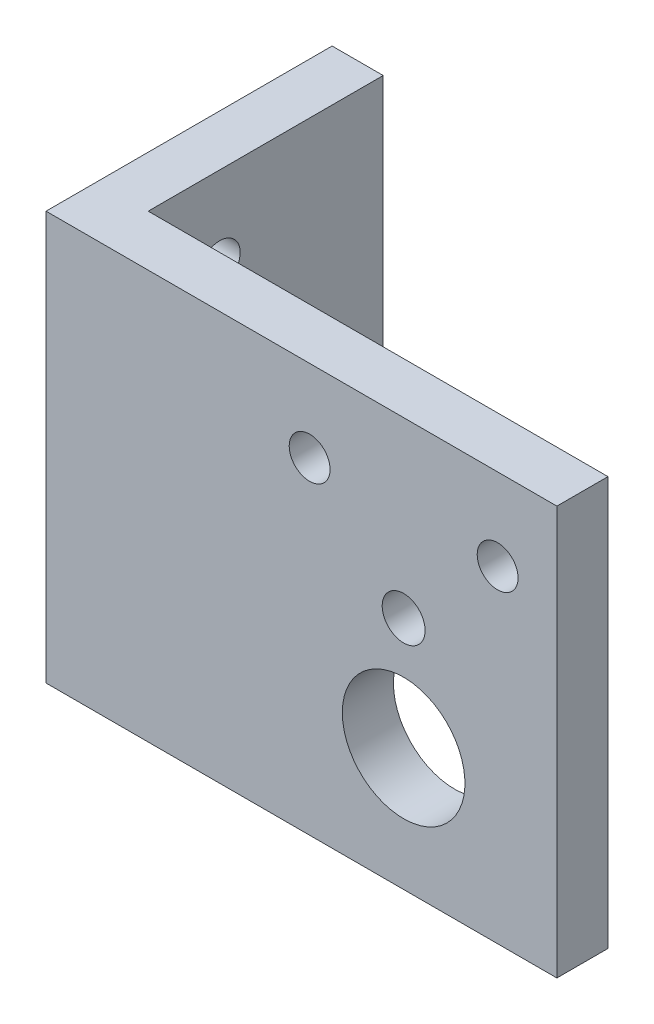
SolidWorks part; units mm, degrees
ref_plane "Front Plane" through (0, 0, 0) normal (0, 0, 1) x (1, 0, 0)
ref_plane "Top Plane" through (0, 0, 0) normal (0, 1, 0) x (1, 0, 0)
ref_plane "Right Plane" through (0, 0, 0) normal (1, 0, 0) x (0, 0, -1)
sketch "Sketch1" plane through (0, 0, 0) normal (0, 1, 0) x (1, 0, 0)
  line L0 (0, 0) -> (50, 0)
  line L1 (50, 0) -> (50, 5)
  line L2 (50, 5) -> (5, 5)
  line L3 (5, 5) -> (5, 35)
  line L4 (5, 35) -> (0, 35)
  line L5 (0, 35) -> (0, 0)
  dimension "D1" = 50
  dimension "D2" = 5
  dimension "D3" = 35
  dimension "D4" = 5
extrude "Boss-Extrude2" add sketch "Sketch1" along normal blind 40 contours L5 L0 L1 L2 L3 L4
sketch "Sketch3" plane through (0, 0, -5) normal (0, 0, -1) x (-1, 0, 0)
  line L0 (-50, 40) -> (-50, 0) construction
  line L1 (-50, 20) -> (-22.4036, 20) construction
  circle A0 centre (-35, 12) radius 6
  circle A1 centre (-35, 23) radius 2.1
  circle A2 centre (-44.2, 32) radius 2
  circle A3 centre (-25.8, 32) radius 2
  dimension "D4" = 12
  dimension "D5" = 4.2
  dimension "D8" = 4
  dimension "D9" = 4
  dimension "D1" = 15
  dimension "D2" = 15
  dimension "D3" = 11
  dimension "D6" = 5.8
  dimension "D7" = 18.4
extrude "Cut-Extrude1" cut sketch "Sketch3" against normal through all
sketch "Sketch4" plane through (5, 0, 0) normal (1, 0, 0) x (0, 0, -1)
  line L0 (5, 40) -> (12, 40)
  line L1 (5, 40) -> (35, 40) construction
  line L2 (5, 40) -> (5, 0) construction
  line L3 (12, 32) -> (12, 7.9155) construction
  line L4 (12, 19.9577) -> (20, 19.9577) construction
  circle A3 centre (12, 32) radius 2
  circle A4 centre (12, 8) radius 2
  circle A6 centre (20, 19.9577) radius 2
  dimension "D2" = 4
  dimension "D3" = 7
  dimension "D1" = 24
extrude "Cut-Extrude3" cut sketch "Sketch4" against normal blind 10 contours A3 | A4 region at (5, 32, -12)
ref_plane "Plane1" through (0, 20, 0) normal (0, 1, 0) x (1, 0, 0)
sketch "Sketch7" plane through (0, 20, 0) normal (0, 1, 0) x (1, 0, 0)
  line L0 (5, 20) -> (20, 5)
  line L1 (5, 5) -> (5, 35) construction
  line L2 (50, 5) -> (5, 5) construction
  dimension "D1" = 15
  dimension "D2" = 15
rib "Rib3" sketch "Sketch7" sketch "Sketch7" thickness 10 extrusion direction parallel to sketch draft on no parameters "D1"=10
sketch "Sketch8" plane through (5, 0, 0) normal (1, 0, 0) x (0, 0, -1)
  line L0 (5, 0) -> (35, 0) construction
  line L1 (35, 40) -> (28, 40)
  line L2 (35, 40) -> (35, 0)
  line L3 (35, 0) -> (28, 0)
  line L4 (28, 40) -> (28, 0)
  point P4 (28, 0)
  dimension "D1" = 7
extrude "Cut-Extrude4" cut sketch "Sketch8" against normal through all
sketch "Sketch9" plane through (5, 0, 0) normal (1, 0, 0) x (0, 0, -1)
  line L0 (12, 32) -> (12, 8) construction
  line L1 (12, 20) -> (20, 20) construction
  circle A0 centre (20, 20) radius 3.25
  dimension "D1" = 6.5
  dimension "D2" = 8
extrude "Cut-Extrude5" cut sketch "Sketch9" along normal through all
sketch "Sketch10" plane through (5, 0, 0) normal (1, 0, 0) x (0, 0, -1)
  line L0 (12, 32) -> (12, 8) construction
  line L1 (12, 20) -> (20, 20) construction
  circle A0 centre (20, 20) radius 2
  dimension "D1" = 8
extrude "Cut-Extrude6" cut sketch "Sketch10" against normal through all
